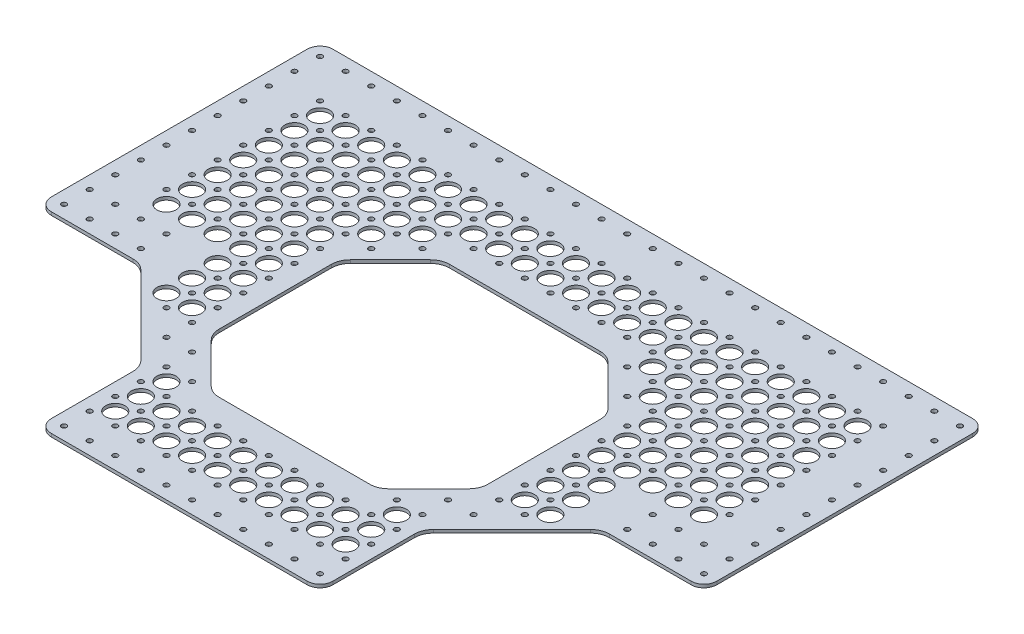
SolidWorks part; units mm, degrees
material "6061 Alloy"
ref_plane "Front Plane" through (0, 0, 0) normal (0, 0, 1) x (1, 0, 0)
ref_plane "Top Plane" through (0, 0, 0) normal (0, 1, 0) x (1, 0, 0)
ref_plane "Right Plane" through (0, 0, 0) normal (1, 0, 0) x (0, 0, -1)
sketch "Sketch1" plane through (0, 0, 0) normal (0, 1, 0) x (1, 0, 0)
  line L0 (0, 0) -> (0, 101.6)
  line L1 (0, 101.6) -> (279.4, 101.6)
  line L2 (279.4, 101.6) -> (279.4, 0)
  line L3 (279.4, 0) -> (368.3045, -88.9045)
  line L4 (368.3045, -88.9045) -> (469.9045, -88.9045)
  line L5 (469.9045, -88.9045) -> (469.9045, -419.1045)
  line L6 (469.9045, -419.1045) -> (368.3045, -419.1045)
  line L7 (368.3045, -419.1045) -> (279.4, -508.0091)
  line L8 (279.4, -508.0091) -> (279.4, -609.6091)
  line L9 (279.4, -609.6091) -> (0, -609.6091)
  line L10 (0, -609.6091) -> (0, -508.0091)
  line L11 (0, -508.0091) -> (-88.9045, -419.1045)
  line L12 (-88.9045, -419.1045) -> (-190.5045, -419.1045)
  line L13 (-190.5045, -419.1045) -> (-190.5045, -88.9045)
  line L14 (-190.5045, -88.9045) -> (-88.9045, -88.9045)
  line L15 (-88.9045, -88.9045) -> (0, 0)
  line L16 (-190.5045, -88.9045) -> (-177.8045, -88.9045)
  line L17 (-177.8045, -88.9045) -> (-177.8045, -419.1045) construction
  line L18 (-177.8045, -419.1045) -> (-190.5045, -419.1045)
  line L19 (-177.8045, -101.6045) -> (-177.8045, -127.0045) construction
  line L20 (139.7, -898.4) -> (139.7, 49101.6) construction
  line L21 (-966.4523, 88.9) -> (49033.5477, 88.9) construction
  line L22 (12.7, 88.9) -> (38.1, 88.9) construction
  line L23 (-1190.5045, -254.0045) -> (48809.4955, -254.0045) construction
  line L24 (-190.5045, -368.3045) -> (-88.9045, -368.3045) construction
  line L25 (-88.9045, -368.3045) -> (-88.9045, -419.1045) construction
  line L26 (-101.6045, -406.4045) -> (-127.0045, -406.4045) construction
  line L27 (-101.6045, -381.0045) -> (-127.0045, -381.0045) construction
  line L28 (-1102.5698, -114.3045) -> (48897.4302, -114.3045) construction
  line L29 (-1089.6596, -165.1045) -> (48910.3404, -165.1045) construction
  line L30 (-177.8045, -127.0045) -> (-152.4045, -127.0045) construction
  circle A0 centre (-177.8045, -101.6045) radius 2.54
  circle A1 centre (-177.8045, -127.0045) radius 2.54
  circle A2 centre (-177.8045, -152.4045) radius 2.54
  circle A3 centre (-177.8045, -177.8045) radius 2.54
  circle A4 centre (-177.8045, -203.2045) radius 2.54
  circle A5 centre (-177.8045, -228.6045) radius 2.54
  circle A6 centre (-177.8045, -254.0045) radius 2.54
  circle A7 centre (-177.8045, -279.4045) radius 2.54
  circle A8 centre (-177.8045, -304.8045) radius 2.54
  circle A9 centre (-177.8045, -330.2045) radius 2.54
  circle A10 centre (-177.8045, -355.6045) radius 2.54
  circle A11 centre (-177.8045, -381.0045) radius 2.54
  circle A12 centre (-177.8045, -406.4045) radius 2.54
  circle A13 centre (457.2045, -406.4045) radius 2.54
  circle A14 centre (457.2045, -381.0045) radius 2.54
  circle A15 centre (457.2045, -355.6045) radius 2.54
  circle A16 centre (457.2045, -330.2045) radius 2.54
  circle A17 centre (457.2045, -304.8045) radius 2.54
  circle A18 centre (457.2045, -279.4045) radius 2.54
  circle A19 centre (457.2045, -254.0045) radius 2.54
  circle A20 centre (457.2045, -228.6045) radius 2.54
  circle A21 centre (457.2045, -152.4045) radius 2.54
  circle A22 centre (457.2045, -177.8045) radius 2.54
  circle A23 centre (457.2045, -203.2045) radius 2.54
  circle A24 centre (457.2045, -127.0045) radius 2.54
  circle A25 centre (457.2045, -101.6045) radius 2.54
  circle A26 centre (12.7, 88.9) radius 2.54
  circle A27 centre (38.1, 88.9) radius 2.54
  circle A28 centre (63.5, 88.9) radius 2.54
  circle A29 centre (88.9, 88.9) radius 2.54
  circle A30 centre (114.3, 88.9) radius 2.54
  circle A31 centre (139.7, 88.9) radius 2.54
  circle A32 centre (165.1, 88.9) radius 2.54
  circle A33 centre (190.5, 88.9) radius 2.54
  circle A34 centre (215.9, 88.9) radius 2.54
  circle A35 centre (241.3, 88.9) radius 2.54
  circle A36 centre (266.7, 88.9) radius 2.54
  circle A37 centre (266.7, -596.9091) radius 2.54
  circle A38 centre (241.3, -596.9091) radius 2.54
  circle A39 centre (215.9, -596.9091) radius 2.54
  circle A40 centre (190.5, -596.9091) radius 2.54
  circle A41 centre (165.1, -596.9091) radius 2.54
  circle A42 centre (139.7, -596.9091) radius 2.54
  circle A43 centre (114.3, -596.9091) radius 2.54
  circle A44 centre (88.9, -596.9091) radius 2.54
  circle A45 centre (63.5, -596.9091) radius 2.54
  circle A46 centre (38.1, -596.9091) radius 2.54
  circle A47 centre (12.7, -596.9091) radius 2.54
  circle A48 centre (-101.6045, -381.0045) radius 2.54
  circle A49 centre (-101.6045, -406.4045) radius 2.54
  circle A50 centre (381.0045, -406.4045) radius 2.54
  circle A51 centre (381.0045, -381.0045) radius 2.54
  circle A52 centre (-127.0045, -406.4045) radius 2.54
  circle A53 centre (-152.4045, -406.4045) radius 2.54
  circle A54 centre (-127.0045, -381.0045) radius 2.54
  circle A55 centre (-152.4045, -381.0045) radius 2.54
  circle A56 centre (431.8045, -381.0045) radius 2.54
  circle A57 centre (406.4045, -381.0045) radius 2.54
  circle A58 centre (431.8045, -406.4045) radius 2.54
  circle A59 centre (406.4045, -406.4045) radius 2.54
  circle A60 centre (-152.4045, -127.0045) radius 2.54
  circle A61 centre (-152.4045, -152.4045) radius 2.54
  circle A62 centre (-127.0045, -127.0045) radius 2.54
  circle A63 centre (-127.0045, -152.4045) radius 2.54
  circle A64 centre (-101.6045, -127.0045) radius 2.54
  circle A65 centre (-101.6045, -152.4045) radius 2.54
  circle A66 centre (-76.2045, -127.0045) radius 2.54
  circle A67 centre (-76.2045, -152.4045) radius 2.54
  circle A68 centre (-50.8045, -127.0045) radius 2.54
  circle A69 centre (-50.8045, -152.4045) radius 2.54
  circle A70 centre (-25.4045, -127.0045) radius 2.54
  circle A71 centre (-25.4045, -152.4045) radius 2.54
  circle A72 centre (-0.0045, -127.0045) radius 2.54
  circle A73 centre (-0.0045, -152.4045) radius 2.54
  circle A74 centre (25.3955, -127.0045) radius 2.54
  circle A75 centre (25.3955, -152.4045) radius 2.54
  circle A76 centre (50.7955, -127.0045) radius 2.54
  circle A77 centre (50.7955, -152.4045) radius 2.54
  circle A78 centre (76.1955, -127.0045) radius 2.54
  circle A79 centre (76.1955, -152.4045) radius 2.54
  circle A80 centre (101.5955, -127.0045) radius 2.54
  circle A81 centre (101.5955, -152.4045) radius 2.54
  circle A82 centre (126.9955, -127.0045) radius 2.54
  circle A83 centre (126.9955, -152.4045) radius 2.54
  circle A84 centre (152.3955, -127.0045) radius 2.54
  circle A85 centre (152.3955, -152.4045) radius 2.54
  circle A86 centre (177.7955, -127.0045) radius 2.54
  circle A87 centre (177.7955, -152.4045) radius 2.54
  circle A88 centre (203.1955, -127.0045) radius 2.54
  circle A89 centre (203.1955, -152.4045) radius 2.54
  circle A90 centre (228.5955, -127.0045) radius 2.54
  circle A91 centre (228.5955, -152.4045) radius 2.54
  circle A92 centre (253.9955, -127.0045) radius 2.54
  circle A93 centre (253.9955, -152.4045) radius 2.54
  circle A94 centre (279.3955, -127.0045) radius 2.54
  circle A95 centre (279.3955, -152.4045) radius 2.54
  circle A96 centre (304.7955, -127.0045) radius 2.54
  circle A97 centre (304.7955, -152.4045) radius 2.54
  circle A98 centre (330.1955, -127.0045) radius 2.54
  circle A99 centre (330.1955, -152.4045) radius 2.54
  circle A100 centre (355.5955, -127.0045) radius 2.54
  circle A101 centre (355.5955, -152.4045) radius 2.54
  circle A102 centre (380.9955, -127.0045) radius 2.54
  circle A103 centre (380.9955, -152.4045) radius 2.54
  circle A104 centre (406.3955, -127.0045) radius 2.54
  circle A105 centre (406.3955, -152.4045) radius 2.54
  circle A106 centre (431.7955, -127.0045) radius 2.54
  circle A107 centre (431.7955, -152.4045) radius 2.54
  point P50 (139.7, 101.6)
  point P105 (-190.5045, -254.0045)
  dimension "D11" = 5.08
  dimension "D16" = 5.08
  dimension "D21" = 5.08
  dimension "D22" = 5.08
  dimension "D1" = 135
  dimension "D2" = 135
  dimension "D3" = 135
  dimension "D4" = 135
  dimension "D5" = 101.6
  dimension "D6" = 279.4
  dimension "D7" = 330.2
  dimension "D8" = 101.6
  dimension "D9" = 125.73
  dimension "D10" = 12.7
  dimension "D12" = 12.7
  dimension "D13" = 25.4
  dimension "D15" = 12.7
  dimension "D17" = 12.7
  dimension "D18" = 25.4
  dimension "D19" = 101.6
  dimension "D20" = 50.8
  dimension "D23" = 12.7
  dimension "D24" = 12.7
  dimension "D25" = 12.7
  dimension "D26" = 12.7
  dimension "D27" = 25.4
  dimension "D28" = 25.4
  dimension "D29" = 25.4
  dimension "D30" = 50.8
  dimension "D31" = 25.4
  dimension "D14" = 13
extrude "Boss-Extrude1" add sketch "Sketch1" along normal blind 3.175 contours L15 L14 L13 L12 L11 L10 L9 L8 L7 L6 L5 L4 L3 L2 L1 L0 A107 A106 A105 A104 A103 A102 A101 A100 A99 A98 A97 A96 A95 A94 A93 A92 region at (139.7, 0, 254.2329)
sketch "Sketch2" plane through (0, 0, -101.6) normal (0, 0, -1) x (-1, 0, 0)
  line L1 (-510.5355, -12.7) -> (251.4645, -12.7)
  line L2 (-510.5355, -12.7) -> (-510.5355, 12.7)
  line L3 (-510.5355, 12.7) -> (251.4645, 12.7)
  line L4 (251.4645, -12.7) -> (251.4645, 12.7)
  line L5 (-510.5355, -12.7) -> (251.4645, 12.7) construction
  line L6 (-510.5355, 12.7) -> (251.4645, -12.7) construction
  point P0 (-129.5355, 0)
  dimension "D1" = 762
  dimension "D2" = 25.4
extrude "Cut-Extrude1" cut sketch "Sketch2" against normal blind 241.3
sketch "Sketch3" plane through (0, 3.175, 0) normal (0, 1, 0) x (1, 0, 0)
  line L0 (-990.1544, -317.5045) -> (49009.8456, -317.5045) construction
  line L1 (-88.9045, -419.1045) -> (-190.5045, -419.1045) construction
  line L2 (-925.1076, -514.3545) -> (49074.8924, -514.3545) construction
  line L3 (139.7, 330.1887) -> (139.7, -609.6091) construction
  line L12 (6.35, -495.3045) -> (273.05, -495.3045)
  line L13 (279.4, -609.6091) -> (0, -609.6091) construction
  line L14 (0, -609.6091) -> (0, -508.0091) construction
  line L15 (6.35, -495.3045) -> (6.35, -317.5045)
  line L16 (6.35, -317.5045) -> (273.05, -317.5045)
  line L17 (273.05, -495.3045) -> (273.05, -317.5045)
  line L18 (6.35, -495.3045) -> (273.05, -317.5045) construction
  line L19 (6.35, -317.5045) -> (273.05, -495.3045) construction
  point P5 (139.7, -406.4045)
  point P9 (139.7, -139.7102)
  point P19 (139.7, -139.7102)
  dimension "D1" = 101.6
  dimension "D2" = 95.25
  dimension "D3" = 177.8
  dimension "D4" = 266.7
  dimension "D6" = 139.7
extrude "Cut-Extrude2" cut sketch "Sketch3" against normal blind 3.175
sketch "Sketch4" plane through (0, 3.175, 0) normal (0, 1, 0) x (1, 0, 0)
  line L0 (222.25, -495.3045) -> (273.05, -444.5045)
  line L1 (6.35, -495.3045) -> (273.05, -495.3045) construction
  line L2 (273.05, -495.3045) -> (273.05, -317.5045) construction
  line L3 (222.25, -495.3045) -> (273.05, -495.3045)
  line L4 (273.05, -495.3045) -> (273.05, -444.5045)
  line L5 (139.7, 369.2915) -> (139.7, -648.6915) construction
  line L7 (279.4, -508.0091) -> (279.4, -609.6091) construction
  line L8 (6.35, -495.3045) -> (6.35, -444.5045)
  line L9 (57.15, -495.3045) -> (6.35, -495.3045)
  line L10 (57.15, -495.3045) -> (6.35, -444.5045)
  point P10 (139.7, -139.7)
  dimension "D1" = 135
  dimension "D2" = 50.8
  dimension "D3" = 139.7
extrude "Boss-Extrude2" add sketch "Sketch4" against normal blind 3.175
sketch "Sketch7" plane through (0, 3.175, 0) normal (0, 1, 0) x (1, 0, 0)
  line L0 (6.35, -317.5045) -> (57.15, -266.7045)
  line L1 (57.15, -266.7045) -> (222.25, -266.7045)
  line L2 (222.25, -266.7045) -> (273.05, -317.5045)
  line L3 (273.05, -317.5045) -> (6.35, -317.5045) construction
  line L4 (6.35, -317.5045) -> (273.05, -317.5045)
  dimension "D1" = 165.1
  dimension "D2" = 45
  dimension "D3" = 45
extrude "Cut-Extrude3" cut sketch "Sketch7" against normal blind 3.175
sketch "Sketch8" plane through (0, 3.175, 0) normal (0, 1, 0) x (1, 0, 0)
  line L0 (-88.9045, -419.1045) -> (-190.5045, -419.1045) construction
  line L1 (0, -609.6091) -> (0, -508.0091) construction
  line L2 (12.7, -596.9091) -> (12.7, -571.5091) construction
  line L3 (279.4, -508.0091) -> (279.4, -609.6091) construction
  line L4 (76.1955, -533.4) -> (101.5955, -533.4) construction
  line L5 (292.1, -292.1091) -> (292.1, -317.5091) construction
  line L6 (-190.5045, -419.1045) -> (-190.5045, -139.7) construction
  line L7 (-190.5045, -139.7) -> (469.9045, -139.7) construction
  line L8 (-127.0045, -203.2) -> (-101.6045, -203.2) construction
  line L9 (-127.0045, -203.2) -> (-127.0045, -228.6) construction
  line L10 (-25.4045, -381) -> (-50.8045, -381) construction
  line L11 (50.7955, -533.4) -> (25.3955, -533.4) construction
  line L12 (228.5955, -533.4) -> (253.9955, -533.4) construction
  line L13 (25.3955, -533.4) -> (25.3955, -508) construction
  line L14 (253.9955, -533.4) -> (253.9955, -508) construction
  line L15 (330.1955, -431.8) -> (304.7955, -431.8) construction
  line L16 (304.7955, -279.4) -> (279.3955, -279.4) construction
  circle A0 centre (12.7, -596.9091) radius 2.54
  circle A1 centre (12.7, -571.5091) radius 2.54
  circle A2 centre (12.7, -546.1091) radius 2.54
  circle A3 centre (12.7, -520.7091) radius 2.54
  circle A4 centre (12.7, -495.3091) radius 2.54
  circle A5 centre (12.7, -469.9091) radius 2.54
  circle A12 centre (12.7, -292.1091) radius 2.54
  circle A13 centre (12.7, -266.7091) radius 2.54
  circle A14 centre (12.7, -241.3091) radius 2.54
  circle A15 centre (12.7, -215.9091) radius 2.54
  circle A16 centre (12.7, -190.5091) radius 2.54
  circle A19 centre (38.1, -190.5091) radius 2.54
  circle A20 centre (38.1, -215.9091) radius 2.54
  circle A21 centre (38.1, -241.3091) radius 2.54
  circle A22 centre (38.1, -266.7091) radius 2.54
  circle A30 centre (38.1, -495.3091) radius 2.54
  circle A31 centre (38.1, -520.7091) radius 2.54
  circle A32 centre (38.1, -546.1091) radius 2.54
  circle A33 centre (38.1, -571.5091) radius 2.54
  circle A35 centre (63.5, -190.5091) radius 2.54
  circle A36 centre (63.5, -215.9091) radius 2.54
  circle A37 centre (63.5, -241.3091) radius 2.54
  circle A47 centre (63.5, -520.7091) radius 2.54
  circle A48 centre (63.5, -546.1091) radius 2.54
  circle A49 centre (63.5, -571.5091) radius 2.54
  circle A51 centre (88.9, -190.5091) radius 2.54
  circle A52 centre (88.9, -215.9091) radius 2.54
  circle A53 centre (88.9, -241.3091) radius 2.54
  circle A63 centre (88.9, -520.7091) radius 2.54
  circle A64 centre (88.9, -546.1091) radius 2.54
  circle A65 centre (88.9, -571.5091) radius 2.54
  circle A67 centre (114.3, -190.5091) radius 2.54
  circle A68 centre (114.3, -215.9091) radius 2.54
  circle A69 centre (114.3, -241.3091) radius 2.54
  circle A79 centre (114.3, -520.7091) radius 2.54
  circle A80 centre (114.3, -546.1091) radius 2.54
  circle A81 centre (114.3, -571.5091) radius 2.54
  circle A83 centre (139.7, -190.5091) radius 2.54
  circle A84 centre (139.7, -215.9091) radius 2.54
  circle A85 centre (139.7, -241.3091) radius 2.54
  circle A95 centre (139.7, -520.7091) radius 2.54
  circle A96 centre (139.7, -546.1091) radius 2.54
  circle A97 centre (139.7, -571.5091) radius 2.54
  circle A99 centre (165.1, -190.5091) radius 2.54
  circle A100 centre (165.1, -215.9091) radius 2.54
  circle A101 centre (165.1, -241.3091) radius 2.54
  circle A111 centre (165.1, -520.7091) radius 2.54
  circle A112 centre (165.1, -546.1091) radius 2.54
  circle A113 centre (165.1, -571.5091) radius 2.54
  circle A115 centre (190.5, -190.5091) radius 2.54
  circle A116 centre (190.5, -215.9091) radius 2.54
  circle A117 centre (190.5, -241.3091) radius 2.54
  circle A127 centre (190.5, -520.7091) radius 2.54
  circle A128 centre (190.5, -546.1091) radius 2.54
  circle A129 centre (190.5, -571.5091) radius 2.54
  circle A131 centre (215.9, -190.5091) radius 2.54
  circle A132 centre (215.9, -215.9091) radius 2.54
  circle A133 centre (215.9, -241.3091) radius 2.54
  circle A143 centre (215.9, -520.7091) radius 2.54
  circle A144 centre (215.9, -546.1091) radius 2.54
  circle A145 centre (215.9, -571.5091) radius 2.54
  circle A147 centre (241.3, -190.5091) radius 2.54
  circle A148 centre (241.3, -215.9091) radius 2.54
  circle A149 centre (241.3, -241.3091) radius 2.54
  circle A150 centre (241.3, -266.7091) radius 2.54
  circle A158 centre (241.3, -495.3091) radius 2.54
  circle A159 centre (241.3, -520.7091) radius 2.54
  circle A160 centre (241.3, -546.1091) radius 2.54
  circle A161 centre (241.3, -571.5091) radius 2.54
  circle A163 centre (266.7, -190.5091) radius 2.54
  circle A164 centre (266.7, -215.9091) radius 2.54
  circle A165 centre (266.7, -241.3091) radius 2.54
  circle A166 centre (266.7, -266.7091) radius 2.54
  circle A167 centre (266.7, -292.1091) radius 2.54
  circle A173 centre (266.7, -469.9091) radius 2.54
  circle A174 centre (266.7, -495.3091) radius 2.54
  circle A175 centre (266.7, -520.7091) radius 2.54
  circle A176 centre (266.7, -546.1091) radius 2.54
  circle A177 centre (266.7, -571.5091) radius 2.54
  circle A179 centre (292.1, -190.5091) radius 2.54
  circle A180 centre (292.1, -215.9091) radius 2.54
  circle A181 centre (292.1, -241.3091) radius 2.54
  circle A182 centre (292.1, -266.7091) radius 2.54
  circle A183 centre (292.1, -292.1091) radius 2.54
  circle A189 centre (292.1, -469.9091) radius 2.54
  circle A195 centre (317.5, -190.5091) radius 2.54
  circle A196 centre (317.5, -215.9091) radius 2.54
  circle A197 centre (317.5, -241.3091) radius 2.54
  circle A198 centre (317.5, -266.7091) radius 2.54
  circle A199 centre (317.5, -292.1091) radius 2.54
  circle A211 centre (342.9, -190.5091) radius 2.54
  circle A212 centre (342.9, -215.9091) radius 2.54
  circle A213 centre (342.9, -241.3091) radius 2.54
  circle A214 centre (342.9, -266.7091) radius 2.54
  circle A215 centre (342.9, -292.1091) radius 2.54
  circle A227 centre (368.3, -190.5091) radius 2.54
  circle A228 centre (368.3, -215.9091) radius 2.54
  circle A229 centre (368.3, -241.3091) radius 2.54
  circle A230 centre (368.3, -266.7091) radius 2.54
  circle A231 centre (368.3, -292.1091) radius 2.54
  circle A243 centre (393.7, -190.5091) radius 2.54
  circle A244 centre (393.7, -215.9091) radius 2.54
  circle A245 centre (393.7, -241.3091) radius 2.54
  circle A246 centre (393.7, -266.7091) radius 2.54
  circle A247 centre (393.7, -292.1091) radius 2.54
  circle A259 centre (419.1, -190.5091) radius 2.54
  circle A260 centre (419.1, -215.9091) radius 2.54
  circle A261 centre (419.1, -241.3091) radius 2.54
  circle A262 centre (419.1, -266.7091) radius 2.54
  circle A263 centre (419.1, -292.1091) radius 2.54
  circle A291 centre (-12.7, -190.5091) radius 2.54
  circle A292 centre (-12.7, -215.9091) radius 2.54
  circle A293 centre (-12.7, -241.3091) radius 2.54
  circle A294 centre (-12.7, -266.7091) radius 2.54
  circle A295 centre (-12.7, -292.1091) radius 2.54
  circle A302 centre (-12.7, -469.9091) radius 2.54
  circle A308 centre (-38.1, -190.5091) radius 2.54
  circle A309 centre (-38.1, -215.9091) radius 2.54
  circle A310 centre (-38.1, -241.3091) radius 2.54
  circle A311 centre (-38.1, -266.7091) radius 2.54
  circle A312 centre (-38.1, -292.1091) radius 2.54
  circle A325 centre (-63.5, -190.5091) radius 2.54
  circle A326 centre (-63.5, -215.9091) radius 2.54
  circle A327 centre (-63.5, -241.3091) radius 2.54
  circle A328 centre (-63.5, -266.7091) radius 2.54
  circle A329 centre (-63.5, -292.1091) radius 2.54
  circle A342 centre (-88.9, -190.5091) radius 2.54
  circle A343 centre (-88.9, -215.9091) radius 2.54
  circle A344 centre (-88.9, -241.3091) radius 2.54
  circle A345 centre (-88.9, -266.7091) radius 2.54
  circle A346 centre (-88.9, -292.1091) radius 2.54
  circle A359 centre (-114.3, -190.5091) radius 2.54
  circle A360 centre (-114.3, -215.9091) radius 2.54
  circle A361 centre (-114.3, -241.3091) radius 2.54
  circle A362 centre (-114.3, -266.7091) radius 2.54
  circle A363 centre (-114.3, -292.1091) radius 2.54
  circle A376 centre (-139.7, -190.5091) radius 2.54
  circle A377 centre (-139.7, -215.9091) radius 2.54
  circle A378 centre (-139.7, -241.3091) radius 2.54
  circle A379 centre (-139.7, -266.7091) radius 2.54
  circle A380 centre (-139.7, -292.1091) radius 2.54
  circle A409 centre (-63.5, -495.3091) radius 2.54 [skipped]
  circle A410 centre (-63.5, -520.7091) radius 2.54 [skipped]
  circle A411 centre (-63.5, -546.1091) radius 2.54 [skipped]
  circle A412 centre (-63.5, -571.5091) radius 2.54 [skipped]
  circle A413 centre (-88.9, -469.9091) radius 2.54 [skipped]
  circle A414 centre (-88.9, -495.3091) radius 2.54 [skipped]
  circle A415 centre (-88.9, -520.7091) radius 2.54 [skipped]
  circle A416 centre (-88.9, -546.1091) radius 2.54 [skipped]
  circle A417 centre (-88.9, -571.5091) radius 2.54 [skipped]
  circle A418 centre (-114.3, -469.9091) radius 2.54 [skipped]
  circle A419 centre (-114.3, -495.3091) radius 2.54 [skipped]
  circle A420 centre (-114.3, -520.7091) radius 2.54 [skipped]
  circle A421 centre (-114.3, -546.1091) radius 2.54 [skipped]
  circle A422 centre (-114.3, -571.5091) radius 2.54 [skipped]
  circle A423 centre (-139.7, -469.9091) radius 2.54 [skipped]
  circle A424 centre (-139.7, -495.3091) radius 2.54 [skipped]
  circle A425 centre (-139.7, -520.7091) radius 2.54 [skipped]
  circle A426 centre (-139.7, -546.1091) radius 2.54 [skipped]
  circle A427 centre (-139.7, -571.5091) radius 2.54 [skipped]
  circle A428 centre (-165.1, -469.9091) radius 2.54 [skipped]
  circle A429 centre (-165.1, -495.3091) radius 2.54 [skipped]
  circle A430 centre (-165.1, -520.7091) radius 2.54 [skipped]
  circle A431 centre (-165.1, -546.1091) radius 2.54 [skipped]
  circle A432 centre (-165.1, -571.5091) radius 2.54 [skipped]
  circle A433 centre (-63.5, -469.9091) radius 2.54 [skipped]
  circle A434 centre (-12.7, -495.3091) radius 2.54 [skipped]
  circle A435 centre (-12.7, -520.7091) radius 2.54 [skipped]
  circle A436 centre (-12.7, -546.1091) radius 2.54 [skipped]
  circle A437 centre (-12.7, -571.5091) radius 2.54 [skipped]
  circle A438 centre (-38.1, -495.3091) radius 2.54 [skipped]
  circle A439 centre (-38.1, -520.7091) radius 2.54 [skipped]
  circle A440 centre (-38.1, -546.1091) radius 2.54 [skipped]
  circle A441 centre (-38.1, -571.5091) radius 2.54 [skipped]
  circle A442 centre (-127.0045, -203.2) radius 9.525
  circle A443 centre (-101.6045, -203.2) radius 9.525
  circle A444 centre (-76.2045, -203.2) radius 9.525
  circle A445 centre (-50.8045, -203.2) radius 9.525
  circle A446 centre (-25.4045, -203.2) radius 9.525
  circle A447 centre (-0.0045, -203.2) radius 9.525
  circle A448 centre (25.3955, -203.2) radius 9.525
  circle A449 centre (50.7955, -203.2) radius 9.525
  circle A450 centre (76.1955, -203.2) radius 9.525
  circle A451 centre (-38.1, -469.9091) radius 2.54 [skipped]
  circle A452 centre (101.5955, -203.2) radius 9.525
  circle A453 centre (126.9955, -203.2) radius 9.525
  circle A454 centre (152.3955, -203.2) radius 9.525
  circle A455 centre (177.7955, -203.2) radius 9.525
  circle A456 centre (203.1955, -203.2) radius 9.525
  circle A457 centre (228.5955, -203.2) radius 9.525
  circle A458 centre (253.9955, -203.2) radius 9.525
  circle A459 centre (279.3955, -203.2) radius 9.525
  circle A460 centre (304.7955, -203.2) radius 9.525
  circle A461 centre (330.1955, -203.2) radius 9.525
  circle A462 centre (355.5955, -203.2) radius 9.525
  circle A463 centre (380.9955, -203.2) radius 9.525
  circle A464 centre (406.3955, -203.2) radius 9.525
  circle A467 centre (-101.6045, -228.6) radius 9.525
  circle A468 centre (-76.2045, -228.6) radius 9.525
  circle A469 centre (-50.8045, -228.6) radius 9.525
  circle A470 centre (-25.4045, -228.6) radius 9.525
  circle A471 centre (-0.0045, -228.6) radius 9.525
  circle A472 centre (25.3955, -228.6) radius 9.525
  circle A473 centre (50.7955, -228.6) radius 9.525
  circle A474 centre (76.1955, -228.6) radius 9.525
  circle A475 centre (101.5955, -228.6) radius 9.525
  circle A476 centre (126.9955, -228.6) radius 9.525
  circle A477 centre (152.3955, -228.6) radius 9.525
  circle A478 centre (177.7955, -228.6) radius 9.525
  circle A479 centre (203.1955, -228.6) radius 9.525
  circle A480 centre (228.5955, -228.6) radius 9.525
  circle A481 centre (253.9955, -228.6) radius 9.525
  circle A482 centre (279.3955, -228.6) radius 9.525
  circle A483 centre (304.7955, -228.6) radius 9.525
  circle A484 centre (330.1955, -228.6) radius 9.525
  circle A485 centre (355.5955, -228.6) radius 9.525
  circle A486 centre (380.9955, -228.6) radius 9.525
  circle A487 centre (406.3955, -228.6) radius 9.525
  circle A490 centre (-101.6045, -254) radius 9.525
  circle A491 centre (-76.2045, -254) radius 9.525
  circle A492 centre (-50.8045, -254) radius 9.525
  circle A493 centre (-25.4045, -254) radius 9.525
  circle A494 centre (-0.0045, -254) radius 9.525
  circle A495 centre (25.3955, -254) radius 9.525
  circle A497 centre (38.1, -292.1091) radius 2.54 [skipped]
  circle A498 centre (63.5, -292.1091) radius 2.54 [skipped]
  circle A499 centre (88.9, -292.1091) radius 2.54 [skipped]
  circle A500 centre (114.3, -292.1091) radius 2.54 [skipped]
  circle A501 centre (139.7, -292.1091) radius 2.54 [skipped]
  circle A502 centre (165.1, -292.1091) radius 2.54 [skipped]
  circle A503 centre (190.5, -292.1091) radius 2.54 [skipped]
  circle A504 centre (241.3, -292.1091) radius 2.54 [skipped]
  circle A505 centre (215.9, -292.1091) radius 2.54 [skipped]
  circle A506 centre (63.5, -266.7091) radius 2.54 [skipped]
  circle A507 centre (88.9, -266.7091) radius 2.54 [skipped]
  circle A508 centre (114.3, -266.7091) radius 2.54 [skipped]
  circle A509 centre (139.7, -266.7091) radius 2.54 [skipped]
  circle A510 centre (165.1, -266.7091) radius 2.54 [skipped]
  circle A511 centre (215.9, -266.7091) radius 2.54 [skipped]
  circle A512 centre (190.5, -266.7091) radius 2.54 [skipped]
  circle A518 centre (12.7, -419.1091) radius 2.54 [skipped]
  circle A519 centre (12.7, -393.7091) radius 2.54 [skipped]
  circle A520 centre (12.7, -368.3091) radius 2.54 [skipped]
  circle A521 centre (12.7, -342.9091) radius 2.54 [skipped]
  circle A522 centre (12.7, -317.5091) radius 2.54 [skipped]
  circle A523 centre (12.7, -444.5091) radius 2.54 [skipped]
  circle A524 centre (292.1, -546.1091) radius 2.54 [skipped]
  circle A525 centre (292.1, -571.5091) radius 2.54 [skipped]
  circle A526 centre (317.5, -520.7091) radius 2.54 [skipped]
  circle A527 centre (317.5, -546.1091) radius 2.54 [skipped]
  circle A528 centre (317.5, -571.5091) radius 2.54 [skipped]
  circle A529 centre (342.9, -520.7091) radius 2.54 [skipped]
  circle A530 centre (342.9, -546.1091) radius 2.54 [skipped]
  circle A531 centre (342.9, -571.5091) radius 2.54 [skipped]
  circle A532 centre (368.3, -520.7091) radius 2.54 [skipped]
  circle A533 centre (368.3, -546.1091) radius 2.54 [skipped]
  circle A534 centre (368.3, -571.5091) radius 2.54 [skipped]
  circle A535 centre (393.7, -520.7091) radius 2.54 [skipped]
  circle A536 centre (393.7, -546.1091) radius 2.54 [skipped]
  circle A537 centre (393.7, -571.5091) radius 2.54 [skipped]
  circle A538 centre (419.1, -520.7091) radius 2.54 [skipped]
  circle A539 centre (419.1, -546.1091) radius 2.54 [skipped]
  circle A540 centre (419.1, -571.5091) radius 2.54 [skipped]
  circle A541 centre (444.5, -520.7091) radius 2.54 [skipped]
  circle A542 centre (444.5, -546.1091) radius 2.54 [skipped]
  circle A543 centre (444.5, -571.5091) radius 2.54 [skipped]
  circle A544 centre (292.1, -520.7091) radius 2.54 [skipped]
  circle A545 centre (317.5, -495.3091) radius 2.54 [skipped]
  circle A546 centre (342.9, -495.3091) radius 2.54 [skipped]
  circle A547 centre (368.3, -495.3091) radius 2.54 [skipped]
  circle A548 centre (393.7, -495.3091) radius 2.54 [skipped]
  circle A549 centre (419.1, -495.3091) radius 2.54 [skipped]
  circle A550 centre (444.5, -495.3091) radius 2.54 [skipped]
  circle A551 centre (292.1, -495.3091) radius 2.54 [skipped]
  circle A552 centre (317.5, -469.9091) radius 2.54 [skipped]
  circle A553 centre (342.9, -469.9091) radius 2.54 [skipped]
  circle A554 centre (368.3, -469.9091) radius 2.54 [skipped]
  circle A555 centre (393.7, -469.9091) radius 2.54 [skipped]
  circle A556 centre (419.1, -469.9091) radius 2.54 [skipped]
  circle A557 centre (444.5, -469.9091) radius 2.54 [skipped]
  circle A558 centre (38.1, -469.9091) radius 2.54 [skipped]
  circle A559 centre (63.5, -469.9091) radius 2.54 [skipped]
  circle A560 centre (88.9, -469.9091) radius 2.54 [skipped]
  circle A561 centre (114.3, -469.9091) radius 2.54 [skipped]
  circle A562 centre (139.7, -469.9091) radius 2.54 [skipped]
  circle A563 centre (165.1, -469.9091) radius 2.54 [skipped]
  circle A564 centre (190.5, -469.9091) radius 2.54 [skipped]
  circle A565 centre (215.9, -469.9091) radius 2.54 [skipped]
  circle A566 centre (241.3, -469.9091) radius 2.54 [skipped]
  circle A567 centre (63.5, -495.3091) radius 2.54 [skipped]
  circle A568 centre (88.9, -495.3091) radius 2.54 [skipped]
  circle A569 centre (114.3, -495.3091) radius 2.54 [skipped]
  circle A570 centre (139.7, -495.3091) radius 2.54 [skipped]
  circle A571 centre (165.1, -495.3091) radius 2.54 [skipped]
  circle A572 centre (190.5, -495.3091) radius 2.54 [skipped]
  circle A573 centre (215.9, -495.3091) radius 2.54 [skipped]
  circle A575 centre (-139.7, -317.5091) radius 2.54
  circle A576 centre (-114.3, -317.5091) radius 2.54
  circle A577 centre (-88.9, -317.5091) radius 2.54
  circle A578 centre (-63.5, -317.5091) radius 2.54
  circle A579 centre (-38.1, -317.5091) radius 2.54
  circle A580 centre (-12.7, -317.5091) radius 2.54
  circle A582 centre (-139.7, -342.9091) radius 2.54
  circle A583 centre (-114.3, -342.9091) radius 2.54
  circle A584 centre (-88.9, -342.9091) radius 2.54
  circle A585 centre (-63.5, -342.9091) radius 2.54
  circle A586 centre (-38.1, -342.9091) radius 2.54
  circle A587 centre (-12.7, -342.9091) radius 2.54
  circle A593 centre (-38.1, -368.3091) radius 2.54
  circle A594 centre (-12.7, -368.3091) radius 2.54
  circle A600 centre (-38.1, -393.7091) radius 2.54
  circle A601 centre (-12.7, -393.7091) radius 2.54
  circle A607 centre (-38.1, -419.1091) radius 2.54
  circle A608 centre (-12.7, -419.1091) radius 2.54
  circle A614 centre (-38.1, -444.5091) radius 2.54
  circle A615 centre (-12.7, -444.5091) radius 2.54
  circle A616 centre (292.1, -317.5091) radius 2.54
  circle A617 centre (317.5, -317.5091) radius 2.54
  circle A618 centre (342.9, -317.5091) radius 2.54
  circle A619 centre (368.3, -317.5091) radius 2.54
  circle A620 centre (393.7, -317.5091) radius 2.54
  circle A621 centre (419.1, -317.5091) radius 2.54
  circle A623 centre (292.1, -342.9091) radius 2.54
  circle A624 centre (317.5, -342.9091) radius 2.54
  circle A625 centre (342.9, -342.9091) radius 2.54
  circle A626 centre (368.3, -342.9091) radius 2.54
  circle A627 centre (393.7, -342.9091) radius 2.54
  circle A628 centre (419.1, -342.9091) radius 2.54
  circle A630 centre (292.1, -368.3091) radius 2.54
  circle A631 centre (317.5, -368.3091) radius 2.54
  circle A637 centre (292.1, -393.7091) radius 2.54
  circle A638 centre (317.5, -393.7091) radius 2.54
  circle A644 centre (292.1, -419.1091) radius 2.54
  circle A645 centre (317.5, -419.1091) radius 2.54
  circle A651 centre (292.1, -444.5091) radius 2.54
  circle A652 centre (317.5, -444.5091) radius 2.54
  circle A658 centre (342.9, -444.5091) radius 2.54 [skipped]
  circle A659 centre (393.7, -444.5091) radius 2.54 [skipped]
  circle A660 centre (419.1, -444.5091) radius 2.54 [skipped]
  circle A661 centre (101.5955, -533.4) radius 9.525
  circle A662 centre (368.3, -444.5091) radius 2.54 [skipped]
  circle A663 centre (393.7, -419.1091) radius 2.54 [skipped]
  circle A664 centre (419.1, -419.1091) radius 2.54 [skipped]
  circle A665 centre (126.9955, -533.4) radius 9.525
  circle A666 centre (368.3, -419.1091) radius 2.54 [skipped]
  circle A667 centre (393.7, -393.7091) radius 2.54 [skipped]
  circle A668 centre (419.1, -393.7091) radius 2.54 [skipped]
  circle A669 centre (152.3955, -533.4) radius 9.525
  circle A670 centre (177.7955, -533.4) radius 9.525
  circle A671 centre (-139.7, -444.5091) radius 2.54 [skipped]
  circle A672 centre (-114.3, -444.5091) radius 2.54 [skipped]
  circle A673 centre (-63.5, -444.5091) radius 2.54 [skipped]
  circle A674 centre (-88.9, -444.5091) radius 2.54 [skipped]
  circle A675 centre (203.1955, -533.4) radius 9.525
  circle A676 centre (-139.7, -393.7091) radius 2.54 [skipped]
  circle A677 centre (-114.3, -393.7091) radius 2.54 [skipped]
  circle A678 centre (228.5955, -533.4) radius 9.525
  circle A679 centre (-139.7, -419.1091) radius 2.54 [skipped]
  circle A680 centre (-114.3, -419.1091) radius 2.54 [skipped]
  circle A681 centre (-88.9, -419.1091) radius 2.54 [skipped]
  circle A685 centre (279.3955, -254) radius 9.525
  circle A686 centre (304.7955, -254) radius 9.525
  circle A687 centre (330.1955, -254) radius 9.525
  circle A688 centre (355.5955, -254) radius 9.525
  circle A689 centre (380.9955, -254) radius 9.525
  circle A690 centre (406.3955, -254) radius 9.525
  circle A693 centre (-101.6045, -279.4) radius 9.525
  circle A694 centre (-76.2045, -279.4) radius 9.525
  circle A695 centre (-50.8045, -279.4) radius 9.525
  circle A696 centre (-25.4045, -279.4) radius 9.525
  circle A697 centre (-0.0045, -279.4) radius 9.525
  circle A709 centre (304.7955, -279.4) radius 9.525
  circle A710 centre (330.1955, -279.4) radius 9.525
  circle A711 centre (355.5955, -279.4) radius 9.525
  circle A712 centre (380.9955, -279.4) radius 9.525
  circle A713 centre (406.3955, -279.4) radius 9.525
  circle A716 centre (-101.6045, -304.8) radius 9.525
  circle A717 centre (-76.2045, -304.8) radius 9.525
  circle A718 centre (-50.8045, -304.8) radius 9.525
  circle A719 centre (-25.4045, -304.8) radius 9.525
  circle A723 centre (76.1955, -304.8) radius 9.525 [skipped]
  circle A724 centre (101.5955, -304.8) radius 9.525 [skipped]
  circle A725 centre (126.9955, -304.8) radius 9.525 [skipped]
  circle A726 centre (152.3955, -304.8) radius 9.525 [skipped]
  circle A727 centre (177.7955, -304.8) radius 9.525 [skipped]
  circle A728 centre (203.1955, -304.8) radius 9.525 [skipped]
  circle A729 centre (228.5955, -304.8) radius 9.525 [skipped]
  circle A730 centre (253.9955, -304.8) radius 9.525 [skipped]
  circle A733 centre (330.1955, -304.8) radius 9.525
  circle A734 centre (355.5955, -304.8) radius 9.525
  circle A735 centre (380.9955, -304.8) radius 9.525
  circle A736 centre (406.3955, -304.8) radius 9.525
  circle A739 centre (-101.6045, -330.2) radius 9.525
  circle A740 centre (-76.2045, -330.2) radius 9.525
  circle A741 centre (-50.8045, -330.2) radius 9.525
  circle A742 centre (-25.4045, -330.2) radius 9.525
  circle A745 centre (50.7955, -330.2) radius 9.525 [skipped]
  circle A746 centre (76.1955, -330.2) radius 9.525 [skipped]
  circle A747 centre (101.5955, -330.2) radius 9.525 [skipped]
  circle A748 centre (126.9955, -330.2) radius 9.525 [skipped]
  circle A749 centre (152.3955, -330.2) radius 9.525 [skipped]
  circle A750 centre (177.7955, -330.2) radius 9.525 [skipped]
  circle A751 centre (203.1955, -330.2) radius 9.525 [skipped]
  circle A752 centre (228.5955, -330.2) radius 9.525 [skipped]
  circle A753 centre (253.9955, -330.2) radius 9.525 [skipped]
  circle A754 centre (279.3955, -330.2) radius 9.525 [skipped]
  circle A756 centre (330.1955, -330.2) radius 9.525
  circle A757 centre (355.5955, -330.2) radius 9.525
  circle A758 centre (380.9955, -330.2) radius 9.525
  circle A759 centre (406.3955, -330.2) radius 9.525
  circle A762 centre (-101.6045, -355.6) radius 9.525
  circle A763 centre (-76.2045, -355.6) radius 9.525
  circle A764 centre (-50.8045, -355.6) radius 9.525
  circle A765 centre (-25.4045, -355.6) radius 9.525
  circle A768 centre (50.7955, -355.6) radius 9.525 [skipped]
  circle A769 centre (76.1955, -355.6) radius 9.525 [skipped]
  circle A770 centre (101.5955, -355.6) radius 9.525 [skipped]
  circle A771 centre (126.9955, -355.6) radius 9.525 [skipped]
  circle A772 centre (152.3955, -355.6) radius 9.525 [skipped]
  circle A773 centre (177.7955, -355.6) radius 9.525 [skipped]
  circle A774 centre (203.1955, -355.6) radius 9.525 [skipped]
  circle A775 centre (228.5955, -355.6) radius 9.525 [skipped]
  circle A776 centre (253.9955, -355.6) radius 9.525 [skipped]
  circle A777 centre (279.3955, -355.6) radius 9.525 [skipped]
  circle A779 centre (330.1955, -355.6) radius 9.525
  circle A780 centre (355.5955, -355.6) radius 9.525
  circle A781 centre (380.9955, -355.6) radius 9.525
  circle A782 centre (406.3955, -355.6) radius 9.525
  circle A788 centre (-25.4045, -381) radius 9.525
  circle A791 centre (50.7955, -381) radius 9.525 [skipped]
  circle A792 centre (76.1955, -381) radius 9.525 [skipped]
  circle A799 centre (253.9955, -381) radius 9.525 [skipped]
  circle A800 centre (279.3955, -381) radius 9.525 [skipped]
  circle A802 centre (330.1955, -381) radius 9.525
  circle A811 centre (-25.4045, -406.4) radius 9.525
  circle A814 centre (50.7955, -406.4) radius 9.525 [skipped]
  circle A815 centre (76.1955, -406.4) radius 9.525 [skipped]
  circle A825 centre (330.1955, -406.4) radius 9.525
  circle A834 centre (-25.4045, -431.8) radius 9.525
  circle A837 centre (50.7955, -431.8) radius 9.525 [skipped]
  circle A838 centre (76.1955, -431.8) radius 9.525 [skipped]
  circle A848 centre (330.1955, -431.8) radius 9.525
  circle A856 centre (-50.8045, -457.2) radius 9.525 [skipped]
  circle A860 centre (50.7955, -457.2) radius 9.525 [skipped]
  circle A861 centre (76.1955, -457.2) radius 9.525 [skipped]
  circle A873 centre (380.9955, -457.2) radius 9.525 [skipped]
  circle A880 centre (-25.4045, -482.6) radius 9.525 [skipped]
  circle A883 centre (50.7955, -482.6) radius 9.525 [skipped]
  circle A884 centre (76.1955, -482.6) radius 9.525 [skipped]
  circle A892 centre (279.3955, -482.6) radius 9.525 [skipped]
  circle A895 centre (355.5955, -482.6) radius 9.525 [skipped]
  circle A904 centre (-0.0045, -508) radius 9.525 [skipped]
  circle A914 centre (253.9955, -508) radius 9.525 [skipped]
  circle A917 centre (330.1955, -508) radius 9.525 [skipped]
  circle A928 centre (25.3955, -533.4) radius 9.525 [skipped]
  circle A929 centre (50.7955, -533.4) radius 9.525
  circle A930 centre (76.1955, -533.4) radius 9.525
  circle A939 centre (304.7955, -533.4) radius 9.525 [skipped]
  circle A951 centre (25.3955, -558.8) radius 9.525 [skipped]
  circle A952 centre (50.7955, -558.8) radius 9.525
  circle A953 centre (76.1955, -558.8) radius 9.525
  circle A954 centre (101.5955, -558.8) radius 9.525
  circle A955 centre (126.9955, -558.8) radius 9.525
  circle A956 centre (152.3955, -558.8) radius 9.525
  circle A957 centre (177.7955, -558.8) radius 9.525
  circle A958 centre (203.1955, -558.8) radius 9.525
  circle A959 centre (228.5955, -558.8) radius 9.525
  circle A962 centre (304.7955, -558.8) radius 9.525 [skipped]
  circle A985 centre (-50.8045, -381) radius 9.525
  circle A992 centre (-127.0045, -228.6) radius 9.525
  circle A993 centre (-127.0045, -254) radius 9.525
  circle A994 centre (-127.0045, -279.4) radius 9.525
  circle A995 centre (-127.0045, -304.8) radius 9.525
  circle A996 centre (-127.0045, -330.2) radius 9.525
  circle A997 centre (-127.0045, -355.6) radius 9.525
  circle A1007 centre (76.1955, -508) radius 9.525 [skipped]
  circle A1008 centre (25.3955, -355.6) radius 9.525 [skipped]
  circle A1009 centre (25.3955, -381) radius 9.525 [skipped]
  circle A1010 centre (25.3955, -406.4) radius 9.525 [skipped]
  circle A1011 centre (25.3955, -431.8) radius 9.525 [skipped]
  circle A1012 centre (25.3955, -457.2) radius 9.525 [skipped]
  circle A1013 centre (279.3955, -457.2) radius 9.525 [skipped]
  circle A1014 centre (101.5955, -381) radius 9.525 [skipped]
  circle A1015 centre (126.9955, -381) radius 9.525 [skipped]
  circle A1016 centre (152.3955, -381) radius 9.525 [skipped]
  circle A1017 centre (177.7955, -381) radius 9.525 [skipped]
  circle A1018 centre (203.1955, -381) radius 9.525 [skipped]
  circle A1019 centre (228.5955, -381) radius 9.525 [skipped]
  circle A1020 centre (101.5955, -406.4) radius 9.525 [skipped]
  circle A1021 centre (126.9955, -406.4) radius 9.525 [skipped]
  circle A1022 centre (152.3955, -406.4) radius 9.525 [skipped]
  circle A1023 centre (177.7955, -406.4) radius 9.525 [skipped]
  circle A1024 centre (203.1955, -406.4) radius 9.525 [skipped]
  circle A1025 centre (228.5955, -406.4) radius 9.525 [skipped]
  circle A1026 centre (101.5955, -431.8) radius 9.525 [skipped]
  circle A1027 centre (126.9955, -431.8) radius 9.525 [skipped]
  circle A1028 centre (152.3955, -431.8) radius 9.525 [skipped]
  circle A1029 centre (177.7955, -431.8) radius 9.525 [skipped]
  circle A1030 centre (203.1955, -431.8) radius 9.525 [skipped]
  circle A1031 centre (228.5955, -431.8) radius 9.525 [skipped]
  circle A1032 centre (101.5955, -457.2) radius 9.525 [skipped]
  circle A1033 centre (126.9955, -457.2) radius 9.525 [skipped]
  circle A1034 centre (152.3955, -457.2) radius 9.525 [skipped]
  circle A1035 centre (177.7955, -457.2) radius 9.525 [skipped]
  circle A1036 centre (203.1955, -457.2) radius 9.525 [skipped]
  circle A1037 centre (228.5955, -457.2) radius 9.525 [skipped]
  circle A1038 centre (101.5955, -482.6) radius 9.525 [skipped]
  circle A1039 centre (126.9955, -482.6) radius 9.525 [skipped]
  circle A1040 centre (152.3955, -482.6) radius 9.525 [skipped]
  circle A1041 centre (177.7955, -482.6) radius 9.525 [skipped]
  circle A1042 centre (203.1955, -482.6) radius 9.525 [skipped]
  circle A1043 centre (228.5955, -482.6) radius 9.525 [skipped]
  circle A1044 centre (101.5955, -508) radius 9.525 [skipped]
  circle A1045 centre (126.9955, -508) radius 9.525 [skipped]
  circle A1046 centre (152.3955, -508) radius 9.525 [skipped]
  circle A1047 centre (177.7955, -508) radius 9.525 [skipped]
  circle A1048 centre (203.1955, -508) radius 9.525 [skipped]
  circle A1049 centre (228.5955, -508) radius 9.525 [skipped]
  circle A1050 centre (253.9955, -406.4) radius 9.525 [skipped]
  circle A1051 centre (279.3955, -406.4) radius 9.525 [skipped]
  circle A1052 centre (253.9955, -431.8) radius 9.525 [skipped]
  circle A1053 centre (253.9955, -457.2) radius 9.525 [skipped]
  circle A1054 centre (279.3955, -431.8) radius 9.525 [skipped]
  circle A1055 centre (253.9955, -482.6) radius 9.525 [skipped]
  circle A1056 centre (304.7955, -355.6) radius 9.525 [skipped]
  circle A1057 centre (304.7955, -381) radius 9.525 [skipped]
  circle A1058 centre (304.7955, -406.4) radius 9.525 [skipped]
  circle A1059 centre (304.7955, -431.8) radius 9.525 [skipped]
  circle A1060 centre (304.7955, -457.2) radius 9.525 [skipped]
  circle A1061 centre (-127.0045, -406.4) radius 9.525 [skipped]
  circle A1062 centre (-101.6045, -406.4) radius 9.525 [skipped]
  circle A1063 centre (-76.2045, -406.4) radius 9.525 [skipped]
  circle A1064 centre (-76.2045, -431.8) radius 9.525 [skipped]
  circle A1065 centre (-101.6045, -431.8) radius 9.525 [skipped]
  circle A1066 centre (-127.0045, -431.8) radius 9.525 [skipped]
  circle A1067 centre (-50.8045, -406.4) radius 9.525
  circle A1068 centre (-139.7, -368.3091) radius 2.54 [skipped]
  circle A1069 centre (-114.3, -368.3091) radius 2.54 [skipped]
  circle A1070 centre (-88.9, -368.3091) radius 2.54 [skipped]
  circle A1071 centre (-88.9, -393.7091) radius 2.54 [skipped]
  circle A1072 centre (-101.6045, -457.2) radius 9.525 [skipped]
  circle A1073 centre (-76.2045, -457.2) radius 9.525 [skipped]
  circle A1074 centre (-101.6045, -482.6) radius 9.525 [skipped]
  circle A1075 centre (-76.2045, -482.6) radius 9.525 [skipped]
  circle A1076 centre (-127.0045, -457.2) radius 9.525 [skipped]
  circle A1077 centre (-127.0045, -482.6) radius 9.525 [skipped]
  circle A1078 centre (-50.8045, -482.6) radius 9.525 [skipped]
  circle A1079 centre (-101.6045, -533.4) radius 9.525 [skipped]
  circle A1080 centre (-76.2045, -533.4) radius 9.525 [skipped]
  circle A1081 centre (-50.8045, -533.4) radius 9.525 [skipped]
  circle A1082 centre (-25.4045, -533.4) radius 9.525 [skipped]
  circle A1083 centre (-0.0045, -533.4) radius 9.525 [skipped]
  circle A1084 centre (-101.6045, -558.8) radius 9.525 [skipped]
  circle A1085 centre (-76.2045, -558.8) radius 9.525 [skipped]
  circle A1086 centre (-50.8045, -558.8) radius 9.525 [skipped]
  circle A1087 centre (-25.4045, -558.8) radius 9.525 [skipped]
  circle A1088 centre (-0.0045, -558.8) radius 9.525 [skipped]
  circle A1089 centre (-50.8045, -431.8) radius 9.525
  circle A1090 centre (25.3955, -533.4) radius 9.525
  circle A1091 centre (25.3955, -558.8) radius 9.525
  circle A1092 centre (253.9955, -533.4) radius 9.525
  circle A1093 centre (-127.0045, -533.4) radius 9.525 [skipped]
  circle A1094 centre (-127.0045, -558.8) radius 9.525 [skipped]
  circle A1095 centre (253.9955, -558.8) radius 9.525
  circle A1096 centre (25.3955, -508) radius 9.525
  circle A1097 centre (-101.6045, -508) radius 9.525 [skipped]
  circle A1098 centre (-76.2045, -508) radius 9.525 [skipped]
  circle A1099 centre (-50.8045, -508) radius 9.525 [skipped]
  circle A1100 centre (-25.4045, -508) radius 9.525 [skipped]
  circle A1101 centre (-127.0045, -508) radius 9.525 [skipped]
  circle A1102 centre (355.5955, -533.4) radius 9.525 [skipped]
  circle A1103 centre (380.9955, -533.4) radius 9.525 [skipped]
  circle A1104 centre (406.3955, -533.4) radius 9.525 [skipped]
  circle A1105 centre (253.9955, -508) radius 9.525
  circle A1106 centre (304.7955, -431.8) radius 9.525
  circle A1107 centre (330.1955, -558.8) radius 9.525 [skipped]
  circle A1108 centre (355.5955, -558.8) radius 9.525 [skipped]
  circle A1109 centre (380.9955, -558.8) radius 9.525 [skipped]
  circle A1110 centre (406.3955, -558.8) radius 9.525 [skipped]
  circle A1111 centre (304.7955, -406.4) radius 9.525
  circle A1112 centre (304.7955, -381) radius 9.525
  circle A1113 centre (304.7955, -355.6) radius 9.525
  circle A1114 centre (304.7955, -330.2) radius 9.525
  circle A1115 centre (304.7955, -304.8) radius 9.525
  circle A1116 centre (279.3955, -279.4) radius 9.525
  circle A1117 centre (253.9955, -254) radius 9.525
  circle A1119 centre (330.1955, -533.4) radius 9.525 [skipped]
  circle A1120 centre (380.9955, -508) radius 9.525 [skipped]
  circle A1121 centre (406.3955, -508) radius 9.525 [skipped]
  circle A1124 centre (355.5955, -508) radius 9.525 [skipped]
  circle A1126 centre (380.9955, -482.6) radius 9.525 [skipped]
  circle A1127 centre (406.3955, -482.6) radius 9.525 [skipped]
  circle A1129 centre (406.3955, -457.2) radius 9.525 [skipped]
  circle A1132 centre (406.3955, -431.8) radius 9.525 [skipped]
  circle A1135 centre (406.3955, -406.4) radius 9.525 [skipped]
  circle A1138 centre (368.3, -368.3091) radius 2.54 [skipped]
  circle A1139 centre (368.3, -393.7091) radius 2.54 [skipped]
  circle A1140 centre (393.7, -368.3091) radius 2.54 [skipped]
  circle A1141 centre (419.1, -368.3091) radius 2.54 [skipped]
  circle A1143 centre (380.9955, -406.4) radius 9.525 [skipped]
  circle A1144 centre (380.9955, -431.8) radius 9.525 [skipped]
  circle A1145 centre (342.9, -368.3091) radius 2.54 [skipped]
  circle A1146 centre (342.9, -393.7091) radius 2.54 [skipped]
  circle A1147 centre (342.9, -419.1091) radius 2.54 [skipped]
  circle A1148 centre (-50.8045, -406.4) radius 9.525 [skipped]
  circle A1149 centre (-50.8045, -431.8) radius 9.525 [skipped]
  circle A1150 centre (-63.5, -419.1091) radius 2.54 [skipped]
  circle A1151 centre (-63.5, -393.7091) radius 2.54 [skipped]
  circle A1152 centre (-63.5, -368.3091) radius 2.54 [skipped]
  circle A1177 centre (12.7, -165.1091) radius 2.54 [skipped]
  circle A1178 centre (-165.1, -215.9091) radius 2.54 [skipped]
  circle A1179 centre (-165.1, -241.3091) radius 2.54 [skipped]
  circle A1180 centre (-165.1, -266.7091) radius 2.54 [skipped]
  circle A1181 centre (-165.1, -292.1091) radius 2.54 [skipped]
  circle A1182 centre (-165.1, -190.5091) radius 2.54 [skipped]
  circle A1183 centre (444.5, -215.9091) radius 2.54 [skipped]
  circle A1184 centre (444.5, -241.3091) radius 2.54 [skipped]
  circle A1185 centre (444.5, -266.7091) radius 2.54 [skipped]
  circle A1186 centre (444.5, -292.1091) radius 2.54 [skipped]
  circle A1187 centre (444.5, -190.5091) radius 2.54 [skipped]
  circle A1188 centre (25.3955, -330.2) radius 9.525 [skipped]
  circle A1189 centre (50.7955, -304.8) radius 9.525 [skipped]
  circle A1190 centre (101.5955, -279.4) radius 9.525 [skipped]
  circle A1191 centre (126.9955, -279.4) radius 9.525 [skipped]
  circle A1192 centre (152.3955, -279.4) radius 9.525 [skipped]
  circle A1193 centre (177.7955, -279.4) radius 9.525 [skipped]
  circle A1194 centre (203.1955, -279.4) radius 9.525 [skipped]
  circle A1195 centre (228.5955, -279.4) radius 9.525 [skipped]
  circle A1196 centre (76.1955, -279.4) radius 9.525 [skipped]
  circle A1197 centre (253.9955, -279.4) radius 9.525 [skipped]
  circle A1198 centre (279.3955, -304.8) radius 9.525 [skipped]
  circle A1199 centre (304.7955, -330.2) radius 9.525 [skipped]
  circle A1200 centre (101.5955, -533.4) radius 9.525 [skipped]
  circle A1201 centre (126.9955, -533.4) radius 9.525 [skipped]
  circle A1202 centre (152.3955, -533.4) radius 9.525 [skipped]
  circle A1203 centre (203.1955, -533.4) radius 9.525 [skipped]
  circle A1204 centre (228.5955, -533.4) radius 9.525 [skipped]
  circle A1205 centre (253.9955, -533.4) radius 9.525 [skipped]
  circle A1206 centre (177.7955, -533.4) radius 9.525 [skipped]
  circle A1207 centre (279.3955, -508) radius 9.525 [skipped]
  circle A1208 centre (304.7955, -482.6) radius 9.525 [skipped]
  circle A1209 centre (50.7955, -508) radius 9.525 [skipped]
  circle A1210 centre (25.3955, -482.6) radius 9.525 [skipped]
  circle A1211 centre (-25.4045, -457.2) radius 9.525 [skipped]
  circle A1212 centre (-0.0045, -482.6) radius 9.525 [skipped]
  circle A1213 centre (25.3955, -508) radius 9.525 [skipped]
  circle A1214 centre (-127.0045, -381) radius 9.525 [skipped]
  circle A1215 centre (-76.2045, -381) radius 9.525 [skipped]
  circle A1216 centre (-101.6045, -381) radius 9.525 [skipped]
  circle A1217 centre (406.3955, -381) radius 9.525 [skipped]
  circle A1220 centre (380.9955, -381) radius 9.525 [skipped]
  circle A1221 centre (-50.8045, -381) radius 9.525 [skipped]
  circle A1222 centre (25.3955, -304.8) radius 9.525 [skipped]
  circle A1223 centre (50.7955, -279.4) radius 9.525 [skipped]
  circle A1224 centre (101.5955, -254) radius 9.525 [skipped]
  circle A1225 centre (126.9955, -254) radius 9.525 [skipped]
  circle A1226 centre (152.3955, -254) radius 9.525 [skipped]
  circle A1227 centre (177.7955, -254) radius 9.525 [skipped]
  circle A1228 centre (203.1955, -254) radius 9.525 [skipped]
  circle A1229 centre (228.5955, -254) radius 9.525 [skipped]
  circle A1230 centre (253.9955, -254) radius 9.525 [skipped]
  circle A1231 centre (279.3955, -279.4) radius 9.525 [skipped]
  circle A1232 centre (304.7955, -304.8) radius 9.525 [skipped]
  circle A1233 centre (304.7955, -508) radius 9.525 [skipped]
  circle A1234 centre (330.1955, -482.6) radius 9.525 [skipped]
  circle A1235 centre (355.5955, -457.2) radius 9.525 [skipped]
  circle A1236 centre (-0.0045, -330.2) radius 9.525 [skipped]
  circle A1237 centre (-0.0045, -355.6) radius 9.525 [skipped]
  circle A1238 centre (-0.0045, -381) radius 9.525 [skipped]
  circle A1239 centre (-0.0045, -406.4) radius 9.525 [skipped]
  circle A1240 centre (-0.0045, -431.8) radius 9.525 [skipped]
  circle A1241 centre (-0.0045, -457.2) radius 9.525 [skipped]
  circle A1242 centre (355.5955, -381) radius 9.525 [skipped]
  circle A1243 centre (355.5955, -406.4) radius 9.525 [skipped]
  circle A1244 centre (355.5955, -431.8) radius 9.525 [skipped]
  circle A1245 centre (330.1955, -457.2) radius 9.525 [skipped]
  circle A1246 centre (76.1955, -254) radius 9.525 [skipped]
  circle A1247 centre (50.7955, -254) radius 9.525 [skipped]
  circle A1248 centre (25.3955, -279.4) radius 9.525 [skipped]
  circle A1249 centre (-0.0045, -304.8) radius 9.525 [skipped]
  circle A1250 centre (279.3955, -558.8) radius 9.525 [skipped]
  circle A1251 centre (279.3955, -533.4) radius 9.525 [skipped]
  circle A1252 centre (253.9955, -533.4) radius 9.525 [skipped]
  circle A1253 centre (253.9955, -558.8) radius 9.525 [skipped]
  dimension "D3" = 5.08
  dimension "D13" = 19.05
  dimension "D19" = 25.4
  dimension "D31" = 25.4
  dimension "D32" = 25.4
  dimension "D1" = 18
  dimension "D2" = 12.7
  dimension "D4" = 25.4
  dimension "D6" = 50.8045
  dimension "D7" = 12.7
  dimension "D9" = 76.1955
  dimension "D10" = 25.4
  dimension "D14" = 63.5
  dimension "D15" = 63.5
  dimension "D17" = 25.4
  dimension "D20" = 25.4
  dimension "D21" = 25.4
  dimension "D23" = 25.4
  dimension "D24" = 25.4
  dimension "D26" = 25.4
  dimension "D28" = 25.4
  dimension "D29" = 25.4
  dimension "D30" = 25.4
  dimension "D5" = 18
  dimension "D8" = 8
  dimension "D12" = 7
  dimension "D11" = 7
  dimension "D18" = 22
  dimension "D16" = 15
  dimension "D22" = 8
  dimension "D25" = 2
  dimension "D27" = 2
extrude "Cut-Extrude5" cut sketch "Sketch8" against normal blind 3.175
fillet "Fillet1" radius 12.7 6 edges at (-190.5045, 1.5875, 419.1045) (0, 1.5875, 609.6091) (279.4, 1.5875, 609.6091) (469.9045, 1.5875, 419.1045) (469.9045, 1.5875, 139.7) (-190.5045, 1.5875, 139.7)
fillet "Fillet2" radius 19.05 12 edges at (0, 1.5875, 508.0091) (-88.9045, 1.5875, 419.1045) (222.25, 1.5875, 266.7045) (273.05, 1.5875, 317.5045) (273.05, 1.5875, 444.5045) (222.25, 1.5875, 495.3045) (57.15, 1.5875, 495.3045) (6.35, 1.5875, 317.5045) (57.15, 1.5875, 266.7045) (6.35, 1.5875, 444.5045) (279.4, 1.5875, 508.0091) (368.3045, 1.5875, 419.1045)
sketch "Sketch9" plane through (0, 3.175, 0) normal (0, -1, 0) x (1, 0, 0)
  line L0 (-1189.9314, 139.7) -> (48810.0686, 139.7) construction
  line L1 (-190.5045, -847.6558) -> (-190.5045, 49152.3442) construction
  line L2 (-177.8045, 139.7) -> (457.2045, 139.7) construction
  line L3 (-190.5045, 406.4045) -> (-190.5045, 152.4) construction
  point P3 (-190.5045, 139.7)
sketch "Sketch11" plane through (0, 0, 0) normal (0, -1, 0) x (1, 0, 0)
  line L0 (6.35, 325.3953) -> (6.35, 436.6138) construction
  line L1 (214.3592, 266.7045) -> (65.0408, 266.7045) construction
  line L4 (273.05, 436.6138) -> (273.05, 325.3953) construction
  circle A0 centre (57.15, 330.2045) radius 2.54
  circle A1 centre (57.15, 431.8045) radius 2.54
  circle A2 centre (222.25, 330.2045) radius 2.54
  circle A3 centre (110.0667, 330.2045) radius 2.54
  circle A4 centre (110.0667, 431.8045) radius 2.54
  circle A5 centre (222.25, 431.8045) radius 2.54
  circle A6 centre (162.9833, 330.2045) radius 2.54
  circle A7 centre (162.9833, 431.8045) radius 2.54
  dimension "D1" = 5.08
  dimension "D2" = 50.8
  dimension "D3" = 101.6
  dimension "D5" = 50.8
  dimension "D7" = 52.9167
  dimension "D4" = 63.5
  dimension "D6" = 52.9167
